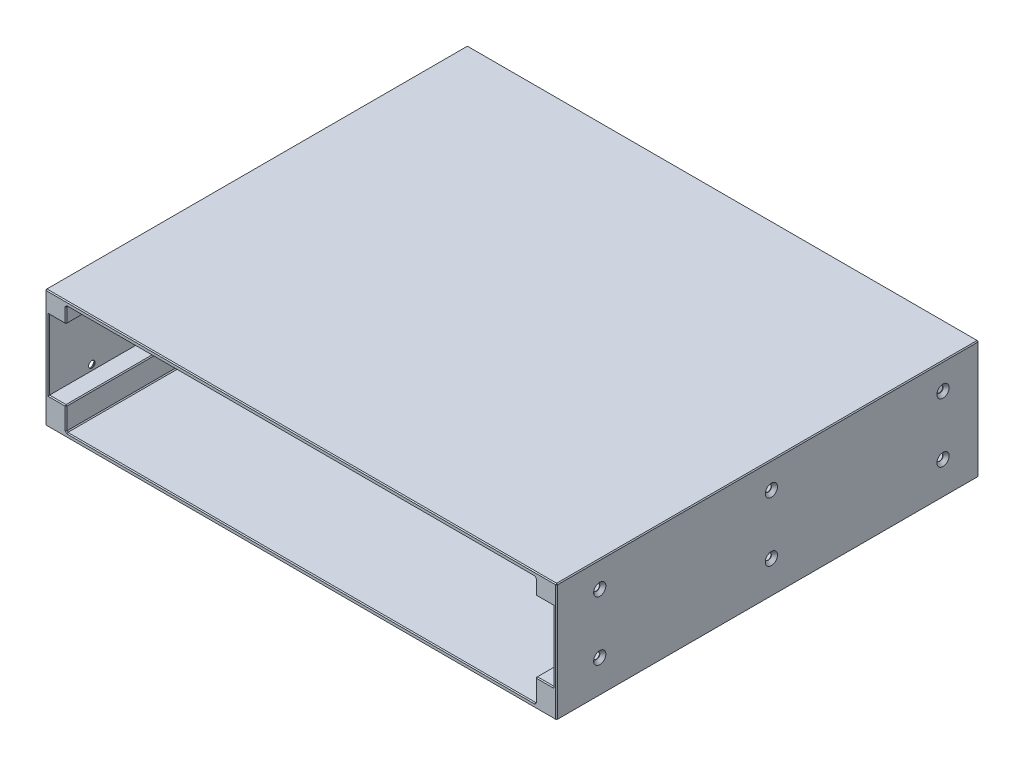
SolidWorks part; units mm, degrees
ref_plane "Front" through (0, 0, 0) normal (0, 0, 1) x (1, 0, 0)
ref_plane "Top" through (0, 0, 0) normal (0, 1, 0) x (1, 0, 0)
ref_plane "Right" through (0, 0, 0) normal (1, 0, 0) x (0, 0, -1)
sketch "Sketch1" plane through (0, 0, 0) normal (0, 0, 1) x (1, 0, 0)
  line L1 (-138, -30) -> (138, -30)
  line L2 (-138, -30) -> (-138, 30)
  line L3 (-138, 30) -> (138, 30)
  line L4 (138, -30) -> (138, 30)
  line L5 (-138, -30) -> (138, 30) construction
  line L6 (-138, 30) -> (138, -30) construction
  point P0 (0, 0)
  dimension "D1" = 276
  dimension "D2" = 60
extrude "Walls" add sketch "Sketch1" along normal blind 230 thin thin type one direction wall 2.5
sketch "Sketch2" plane through (0, 0, 0) normal (0, 0, 1) x (1, 0, 0)
  line L12 (140.5, -32.5) -> (140.5, 32.5)
  line L13 (140.5, 32.5) -> (-140.5, 32.5)
  line L14 (-140.5, 32.5) -> (-140.5, -32.5)
  line L15 (-140.5, -32.5) -> (140.5, -32.5)
  line L16 (140.5, -32.5) -> (140.5, 32.5)
  line L17 (140.5, 32.5) -> (-140.5, 32.5)
  line L18 (-140.5, 32.5) -> (-140.5, -32.5)
  line L19 (-140.5, -32.5) -> (140.5, -32.5)
  dimension "D1" = 0
extrude "Back Plate" add sketch "Sketch2" against normal blind 2
sketch "Sketch7" plane through (138.5, 0, 0) normal (1, 0, 0) x (0, 0, -1)
  line L0 (0, -30) -> (0, 30) construction
  line L1 (0, -17.25) -> (-230, -17.25)
  line L2 (0, -17.25) -> (0, 21.25)
  line L3 (0, 21.25) -> (-230, 21.25)
  line L4 (-230, -17.25) -> (-230, 21.25)
  line L5 (-230, -32.5) -> (-230, 32.5) construction
extrude "Drawer Slide Pocket" cut sketch "Sketch7" against normal up to next
sketch "Sketch8" plane through (138, 0, 0) normal (-1, 0, 0) x (0, 0, 1)
  line L0 (230, 32.5) -> (230, -32.5) construction
  line L1 (0, -30) -> (230, -30)
  line L2 (0, -30) -> (0, -17.25)
  line L3 (0, -17.25) -> (230, -17.25)
  line L4 (230, -30) -> (230, -17.25)
  line L6 (0, 30) -> (230, 30)
  line L7 (0, 30) -> (0, 21.25)
  line L8 (0, 21.25) -> (230, 21.25)
  line L9 (230, 30) -> (230, 21.25)
extrude "Drawer Slide Brackets" add sketch "Sketch8" along normal blind 9
sketch "Sketch9" plane through (140.5, 0, 0) normal (1, 0, 0) x (0, 0, -1)
  point P0 (-206.2857, -14.25)
  point P1 (-206.2857, 18.25)
  point P3 (-112, -14.25)
  point P5 (-112, 18.25)
  point P7 (-17.7143, -14.25)
  point P9 (-17.7143, 18.25)
hole_wizard "CSK for M3 SFHCS1" positions "Sketch9" profile "Sketch10" countersink size "M3" standard "ANSI Metric" end condition up to next
sketch "Sketch10" plane through (140.5, -14.25, 206.2857) normal (0, 1, 0) x (0, 0, -1)
  line L0 (0, 0) -> (0, 2)
  line L1 (0, 2) -> (1.8, 2)
  line L2 (1.7, 1.9) -> (1.7, 1.66)
  line L3 (1.7, 1.66) -> (3.36, 0)
  line L5 (3.36, 0) -> (0, 0)
  line L6 (-1.7, 1.66) -> (-3.36, 0) construction
  line L7 (1.8, 2) -> (1.7, 1.9)
  line L8 (-1.8, 2) -> (-1.7, 1.9) construction
  line L11 (0, -6.35) -> (0, 107.95) construction
  dimension "Thru Hole Dia." = 3.4
  dimension "Thru Hole Depth" = 2
  dimension "Near C'Sink Dia." = 6.72
  dimension "Near C'Sink Angle" = 90
  dimension "Far C'Sink Dia." = 3.6
  dimension "Far C'Sink Angle" = 90
mirror "Drawer Slide Pocket mirror" about plane through (0, 0, 0) normal (1, 0, 0) of "CSK for M3 SFHCS1", "Drawer Slide Pocket", "Drawer Slide Brackets"
sketch "Sketch3" plane through (0, -32.5, 0) normal (0, 1, 0) x (1, 0, 0)
  line L0 (0, 2) -> (0, -114) construction
  line L1 (-114.5192, -23.9808) -> (114.5192, -23.9808) construction
  line L2 (-114.5192, -23.9808) -> (-114.5192, -204.0192) construction
  line L3 (-114.5192, -204.0192) -> (114.5192, -204.0192) construction
  line L4 (114.5192, -23.9808) -> (114.5192, -204.0192) construction
  line L5 (-114.5192, -23.9808) -> (114.5192, -204.0192) construction
  line L6 (-114.5192, -204.0192) -> (114.5192, -23.9808) construction
  line L8 (0, -114) -> (0, -230) construction
  line L10 (-140.5, -23.9808) -> (-114.5192, -23.9808) construction
  line L11 (140.5, 2) -> (-140.5, 2) construction
  line L12 (-114.5192, -23.9808) -> (-114.5192, 2) construction
  line L13 (-57.2596, -23.9808) -> (-57.2596, -15.3205) construction
  line L14 (-114.5192, -32.641) -> (-107.0192, -28.3109)
  line L15 (-107.0192, -28.3109) -> (-107.0192, -19.6506)
  line L16 (-107.0192, -19.6506) -> (-114.5192, -15.3205)
  line L17 (-114.5192, -15.3205) -> (-122.0192, -19.6506)
  line L18 (-122.0192, -19.6506) -> (-122.0192, -28.3109)
  line L19 (-122.0192, -28.3109) -> (-114.5192, -32.641)
  line L20 (-57.2596, -15.3205) -> (-57.2596, -6.6603) construction
  line L21 (0, -114) -> (114.5192, -114) construction
  line L22 (122.0192, -28.3109) -> (114.5192, -32.641)
  line L23 (122.0192, -19.6506) -> (122.0192, -28.3109)
  line L24 (114.5192, -15.3205) -> (122.0192, -19.6506)
  line L25 (107.0192, -19.6506) -> (114.5192, -15.3205)
  line L26 (107.0192, -28.3109) -> (107.0192, -19.6506)
  line L27 (114.5192, -32.641) -> (107.0192, -28.3109)
  line L28 (122.0192, -208.3494) -> (122.0192, -199.6891)
  line L29 (114.5192, -212.6795) -> (122.0192, -208.3494)
  line L30 (107.0192, -208.3494) -> (114.5192, -212.6795)
  line L31 (107.0192, -199.6891) -> (107.0192, -208.3494)
  line L32 (114.5192, -195.359) -> (107.0192, -199.6891)
  line L33 (122.0192, -199.6891) -> (114.5192, -195.359)
  line L34 (-122.0192, -199.6891) -> (-114.5192, -195.359)
  line L35 (-122.0192, -208.3494) -> (-122.0192, -199.6891)
  line L36 (-114.5192, -212.6795) -> (-122.0192, -208.3494)
  line L37 (-107.0192, -208.3494) -> (-114.5192, -212.6795)
  line L38 (-107.0192, -199.6891) -> (-107.0192, -208.3494)
  line L39 (-114.5192, -195.359) -> (-107.0192, -199.6891)
  line L40 (-57.2596, -6.6603) -> (-57.2596, 2) construction
  line L41 (-114.5192, -10.9904) -> (-57.2596, -10.9904) construction
  line L42 (-57.2596, -10.9904) -> (0, -10.9904) construction
  line L43 (-140.5, -230) -> (-140.5, 2) construction
  line L44 (140.5, -230) -> (-140.5, -230) construction
  circle A0 centre (-114.5192, -23.9808) radius 7.5 construction
  point P0 (0, -114)
  dimension "D1" = 15
extrude "Foot Pocket" cut sketch "Sketch3" along normal blind 1.5 draft 45
sketch "Sketch4" plane through (0, 32.5, 0) normal (0, -1, 0) x (1, 0, 0)
  line L20 (-107.2192, 208.2339) -> (-114.5192, 212.4486)
  line L21 (-114.5192, 212.4486) -> (-121.8192, 208.2339)
  line L22 (-121.8192, 208.2339) -> (-121.8192, 199.8046)
  line L23 (-121.8192, 199.8046) -> (-114.5192, 195.5899)
  line L24 (-114.5192, 195.5899) -> (-107.2192, 199.8046)
  line L25 (-107.2192, 199.8046) -> (-107.2192, 208.2339)
  line L26 (-107.2192, 208.2339) -> (-114.5192, 212.4486)
  line L27 (-114.5192, 212.4486) -> (-121.8192, 208.2339)
  line L28 (-121.8192, 208.2339) -> (-121.8192, 199.8046)
  line L29 (-121.8192, 199.8046) -> (-114.5192, 195.5899)
  line L30 (-114.5192, 195.5899) -> (-107.2192, 199.8046)
  line L31 (-107.2192, 199.8046) -> (-107.2192, 208.2339)
  line L38 (-114.5192, 32.4101) -> (-121.8192, 28.1954)
  line L39 (-121.8192, 28.1954) -> (-121.8192, 19.7661)
  line L40 (-121.8192, 19.7661) -> (-114.5192, 15.5514)
  line L41 (-114.5192, 15.5514) -> (-107.2192, 19.7661)
  line L42 (-107.2192, 19.7661) -> (-107.2192, 28.1954)
  line L43 (-107.2192, 28.1954) -> (-114.5192, 32.4101)
  line L44 (-114.5192, 32.4101) -> (-121.8192, 28.1954)
  line L45 (-121.8192, 28.1954) -> (-121.8192, 19.7661)
  line L46 (-121.8192, 19.7661) -> (-114.5192, 15.5514)
  line L47 (-114.5192, 15.5514) -> (-107.2192, 19.7661)
  line L48 (-107.2192, 19.7661) -> (-107.2192, 28.1954)
  line L49 (-107.2192, 28.1954) -> (-114.5192, 32.4101)
  line L56 (114.5192, 212.4486) -> (107.2192, 208.2339)
  line L57 (107.2192, 208.2339) -> (107.2192, 199.8046)
  line L58 (107.2192, 199.8046) -> (114.5192, 195.5899)
  line L59 (114.5192, 195.5899) -> (121.8192, 199.8046)
  line L60 (121.8192, 199.8046) -> (121.8192, 208.2339)
  line L61 (121.8192, 208.2339) -> (114.5192, 212.4486)
  line L62 (114.5192, 212.4486) -> (107.2192, 208.2339)
  line L63 (107.2192, 208.2339) -> (107.2192, 199.8046)
  line L64 (107.2192, 199.8046) -> (114.5192, 195.5899)
  line L65 (114.5192, 195.5899) -> (121.8192, 199.8046)
  line L66 (121.8192, 199.8046) -> (121.8192, 208.2339)
  line L67 (121.8192, 208.2339) -> (114.5192, 212.4486)
  line L74 (121.8192, 19.7661) -> (121.8192, 28.1954)
  line L75 (114.5192, 15.5514) -> (121.8192, 19.7661)
  line L76 (107.2192, 19.7661) -> (114.5192, 15.5514)
  line L77 (107.2192, 28.1954) -> (107.2192, 19.7661)
  line L78 (114.5192, 32.4101) -> (107.2192, 28.1954)
  line L79 (121.8192, 28.1954) -> (114.5192, 32.4101)
  line L80 (121.8192, 19.7661) -> (121.8192, 28.1954)
  line L81 (114.5192, 15.5514) -> (121.8192, 19.7661)
  line L82 (107.2192, 19.7661) -> (114.5192, 15.5514)
  line L83 (107.2192, 28.1954) -> (107.2192, 19.7661)
  line L84 (114.5192, 32.4101) -> (107.2192, 28.1954)
  line L85 (121.8192, 28.1954) -> (114.5192, 32.4101)
  dimension "D1" = 0.2
  dimension "D2" = 0.2
  dimension "D3" = 0.2
  dimension "D4" = 0.2
extrude "Feet" [suppressed] add sketch "Sketch4" against normal blind 1.3 draft 45
chamfer "Deburs 1" distance 0.5 angle 45 34 edges at (-138.5, 2, 230) (-133.75, -17.25, 230) (-129, -17.25, 115) (-129, -23.625, 230) (0, -30, 230) (0, 30, 230) (-133.75, 21.25, 230) (-129, 21.25, 115) (-129, 25.625, 230) (-129, 30, 115) (0, 30, 0) (129, 30, 115) (129, 25.625, 230) (129, 21.25, 115) (133.75, 21.25, 230) (138.5, 2, 230) (133.75, -17.25, 230) (129, -17.25, 115) (129, -23.625, 230) (-129, -30, 115) (0, -30, 0) (129, -30, 115) (140.5, 0, 230) (0, -32.5, 230) (-140.5, 0, 230) (0, 32.5, 230) (-140.5, 0, -2) (-140.5, 32.5, 114) (0, 32.5, -2) (140.5, 32.5, 114) (140.5, 0, -2) (140.5, -32.5, 114) (0, -32.5, -2) (-140.5, -32.5, 114)
chamfer "Deburs 2" distance 0.5 angle 45 4 edges at (129, -23.625, 0) (129, 25.625, 0) (-129, 25.625, 0) (-129, -23.625, 0)
